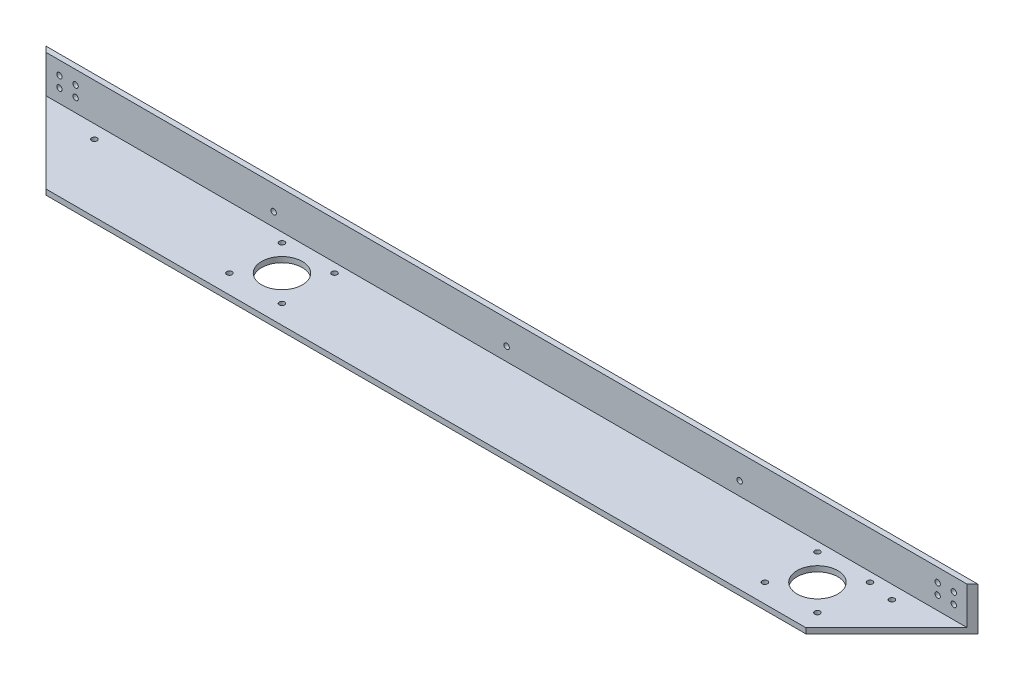
SolidWorks part; units mm, degrees
ref_plane "Front Plane" through (0, 0, 0) normal (0, 0, 1) x (1, 0, 0)
ref_plane "Top Plane" through (0, 0, 0) normal (0, 1, 0) x (1, 0, 0)
ref_plane "Right Plane" through (0, 0, 0) normal (1, 0, 0) x (0, 0, -1)
sketch "Sketch1" plane through (0, 0, 0) normal (1, 0, 0) x (0, 0, -1)
  line L0 (0, 0) -> (-50.8, 0)
  line L1 (-50.8, 0) -> (-50.8, 3.175)
  line L2 (-50.8, 3.175) -> (-3.175, 3.175)
  line L3 (-3.175, 3.175) -> (-3.175, 25.4)
  line L4 (-3.175, 25.4) -> (0, 25.4)
  line L5 (0, 25.4) -> (0, 0)
  dimension "LHeight" = 25.4
  dimension "LWidth" = 50.8
  dimension "LMaterialThickness" = 3.175
  dimension "D1" = 47.625
  dimension "D2" = 22.225
  dimension "D3" = 3.175
extrude "Boss-Extrude1" add sketch "Sketch1" along normal blind 550
chamfer "Chamfer7" distance 50.8 angle 45 1 edges at (0, 1.5875, 50.8)
chamfer "Chamfer8" distance 50.8 angle 45 1 edges at (550, 1.5875, 50.8)
sketch "BotthomHoles-Sketch2" plane through (0, 3.175, 0) normal (0, 1, 0) x (1, 0, 0)
  line L0 (546.825, -3.175) -> (3.175, -3.175) construction
  line L1 (550, 0) -> (0, 0) construction
  circle A0 centre (479.425, -24.175) radius 12
  circle A2 centre (463.925, -8.675) radius 1.5875
  circle A3 centre (494.925, -8.675) radius 1.5875
  circle A6 centre (463.925, -39.675) radius 1.5875
  circle A7 centre (494.925, -39.675) radius 1.5875
  circle A8 centre (39.6875, -11.1125) radius 1.5875
  circle A9 centre (510.3125, -11.1125) radius 1.5875
  circle A10 centre (178.925, -39.675) radius 1.5875
  circle A11 centre (147.925, -39.675) radius 1.5875
  circle A12 centre (178.925, -8.675) radius 1.5875
  circle A13 centre (147.925, -8.675) radius 1.5875
  circle A14 centre (163.425, -24.175) radius 12
  dimension "D9" = 3.175
  dimension "D10" = 24
  dimension "D13" = 3.175
  dimension "D2" = 8.675
  dimension "D5" = 15.5
  dimension "D6" = 31
  dimension "D7" = 15.5
  dimension "D8" = 31
  dimension "D11" = 21
  dimension "D3" = 70.575
  dimension "D4" = 11.1125
  dimension "D12" = 39.6875
  dimension "D14" = 39.6875
  dimension "D15" = 31
  dimension "D16" = 15.5
  dimension "D17" = 316
extrude "BottomHoles-Cut-Extrude1" cut sketch "BotthomHoles-Sketch2" against normal through all
sketch "RightSideHoles-Sketch3" plane through (0, 0, 0) normal (0, 0, -1) x (-1, 0, 0)
  line L0 (-550, 0) -> (-550, 25.4) construction
  circle A0 centre (-538.8875, 17.4625) radius 1.5875
  circle A1 centre (-529.3625, 17.4625) radius 1.5875
  circle A2 centre (-538.8875, 11.1125) radius 1.5875
  circle A3 centre (-529.3625, 11.1125) radius 1.5875
  circle A4 centre (-11.1125, 11.1125) radius 1.5875
  circle A5 centre (-20.6375, 11.1125) radius 1.5875
  circle A6 centre (-20.6375, 17.4625) radius 1.5875
  circle A7 centre (-11.1125, 17.4625) radius 1.5875
  circle A8 centre (-412.5, 11.1125) radius 1.5875
  circle A9 centre (-275, 11.1125) radius 1.5875
  circle A10 centre (-137.5, 11.1125) radius 1.5875
  dimension "D4" = 11.1125
  dimension "D7" = 3.175
  dimension "D1" = 11.1125
  dimension "D2" = 20.6375
  dimension "D3" = 7.9375
  dimension "D5" = 11.1125
  dimension "D6" = 20.6375
  dimension "D8" = 137.5
  dimension "D9" = 137.5
  dimension "D10" = 137.5
extrude "RightSideHoles-Cut-Extrude2" cut sketch "RightSideHoles-Sketch3" against normal through all
equation "\"LowerRailWidth\"= 2.00in"
equation "\"LowerRailHeight\"= 1.00in"
equation "\"RailThickness\"= .125in'Spec"
equation "\"SideRailHoleY1FromEdge\"= \"HoleOffsetFromEdge\""
equation "\"SideRailHoleX1FromSide\"= \"HoleOffsetFromSide\""
equation "\"StepperHoleDiameter\"= 24mm"
equation "\"StepperMountingHoleDiameter\"= 3.175mm"
equation "\"SideRailLength\"= 550mm"
equation "\"StepperMountingHoleDistance\"= 31mm'Spec"
equation "\"VSWidth\"= 1.25in'Spec"
equation "\"StepperMountingHoleOffsetFromLeftOrRightSide\"= \"StepperMountingHoleOffsetFromItsSide\" + \"RailThickness\""
equation "\"HoleOffsetFromEdge\"= \"RailThickness\" * 2.5"
equation "\"HoleOffsetFromSide\"= \"RailThickness\" * 3.5"
equation "\"StepperMountingHoleOffsetFromItsSide\"= 5.5mm'Spec"
equation "\"SideRailHoleX2FromSide\"= \"VSWidth\" - \"HoleOffsetFromEdge\" - \"RailThickness\"'Equals 20.6375"
equation "\"FasteningHoleDiameter\"= .125in"
equation "\"SideRailHoleY2FromSide\"= \"HoleOffsetFromSide\""
equation "\"LHeight@Sketch1\"=\"LowerRailHeight\""
equation "\"LWidth@Sketch1\"=\"LowerRailWidth\""
equation "\"D1@Chamfer7\"=\"LowerRailWidth\""
equation "\"D1@Chamfer8\"=\"LowerRailWidth\""
equation "\"D2@BotthomHoles-Sketch2\" = \"StepperMountingHoleOffsetFromLeftOrRightSide\""
equation "\"D5@BotthomHoles-Sketch2\" = \"StepperMountingHoleDistance\" / 2"
equation "\"D6@BotthomHoles-Sketch2\" = \"StepperMountingHoleDistance\""
equation "\"D7@BotthomHoles-Sketch2\" = \"StepperMountingHoleDistance\" / 2"
equation "\"D8@BotthomHoles-Sketch2\" = \"StepperMountingHoleDistance\""
equation "\"D9@BotthomHoles-Sketch2\" = \"StepperMountingHoleDiameter\""
equation "\"D10@BotthomHoles-Sketch2\" = \"StepperHoleDiameter\""
equation "\"D1@RightSideHoles-Sketch3\" = \"SideRailHoleX1FromSide\""
equation "\"D2@RightSideHoles-Sketch3\" = \"SideRailHoleX2FromSide\""
equation "\"D3@RightSideHoles-Sketch3\" = \"SideRailHoleY1FromEdge\""
equation "\"D4@RightSideHoles-Sketch3\" = \"SideRailHoleY2FromSide\""
equation "\"D7@RightSideHoles-Sketch3\" = \"FasteningHoleDiameter\""
equation "\"D1@Boss-Extrude1\"=\"SideRailLength\""
equation "\"D5@RightSideHoles-Sketch3\"=\"SideRailHoleX1FromSide\""
equation "\"D6@RightSideHoles-Sketch3\"=\"SideRailHoleX2FromSide\""
equation "\"BedOverlap\"= 20mm"
equation "\"BedThirdSize\"= 70mm"
equation "\"BedInnerSquareWidth\"= \"BedThirdSize\" * 3'Equals 210"
equation "\"BedInnerSquareLength\"= \"BedInnerSquareWidth\""
equation "\"BedLWidth\"= \"BedThirdSize\" + \"BedOverlap\"'Equals 90"
equation "\"BedLength\"= \"BedInnerSquareLength\" + \"BedLWidth\" * 2 - \"BedOverlap\" * 2 + \"BedIncreasedByLength\"'Equals 350"
equation "\"DistanceBetweenFrontToBackStepperHoles\"= \"BedLength\" - \"DistanceFromBedFrontToFirstLeftStepperHole\"'Equals 316"
equation "\"D3@BotthomHoles-Sketch2\"=\"DistanceFromFrontSideToFirstLeftStepperHole\""
equation "\"DistanceFromBedFrontToFirstLeftStepperHole\"= \"LeadScrewNutPadSize\" + 10mm'Equals 34"
equation "\"DistanceFromFrontSideToBedFront\"= \"RailThickness\" + \"BeltTensionerDepth\" + 10mm'Equals 36.575"
equation "\"20TGT2PulleyDiameter\"= 17.9mm'Spec"
equation "\"BeltTensionerBackWallThickness\"= 4mm"
equation "\"BeltTensionerSpaceBetweenPulleyAndWall\"= 1.5mm"
equation "\"BeltTensionerInnerDepth\"= \"20TGT2PulleyDiameter\" + \"BeltTensionerSpaceBetweenPulleyAndWall\""
equation "\"BeltTensionerDepth\"= \"BeltTensionerBackWallThickness\" + \"BeltTensionerInnerDepth\"'Equals 23.4"
equation "\"BedIncreasedByLength\"= 0mm"
equation "\"LowerCornerBlockWidth\"= \"LowerRailWidth\" - \"RailThickness\" * 2'Room for left front stepper"
equation "\"D4@BotthomHoles-Sketch2\"=\"LowerCornerBlockY1FromSide\""
equation "\"D12@BotthomHoles-Sketch2\"=\"LowerCornerBlockX1FromSide\""
equation "\"D13@BotthomHoles-Sketch2\"=\"FasteningHoleDiameter\""
equation "\"D14@BotthomHoles-Sketch2\"=\"LowerCornerBlockX1FromSide\""
equation "\"LowerCornerBlockX1FromSide\"= \"LowerCornerBlockWidth\" - \"HoleOffsetFromEdge\" + \"RailThickness\""
equation "\"LowerCornerBlockY1FromSide\"= \"HoleOffsetFromSide\""
equation "\"D15@BotthomHoles-Sketch2\"=\"StepperMountingHoleDistance\""
equation "\"D16@BotthomHoles-Sketch2\"=\"StepperMountingHoleDistance\"/2"
equation "\"D17@BotthomHoles-Sketch2\"=\"DistanceBetweenFrontToBackStepperHoles\""
equation "\"DistanceFromFrontSideToFirstLeftStepperHole\"= \"DistanceFromFrontSideToBedFront\" + \"DistanceFromBedFrontToFirstLeftStepperHole\"'Equals 70.575"
equation "\"LeadScrewNutMountingHoleFlangeDiameter\"= 22mm'Spec"
equation "\"LeadScrewNutPadSize\"= \"LeadScrewNutMountingHoleFlangeDiameter\" + 2mm'Equals 24"
equation "\"LeftOrRightEnclosureOffsets\"= \"SideRailLength\" / 4"
equation "\"D8@RightSideHoles-Sketch3\"=\"LeftOrRightEnclosureOffsets\""
equation "\"D9@RightSideHoles-Sketch3\"=\"LeftOrRightEnclosureOffsets\""
equation "\"D10@RightSideHoles-Sketch3\"=\"LeftOrRightEnclosureOffsets\""
